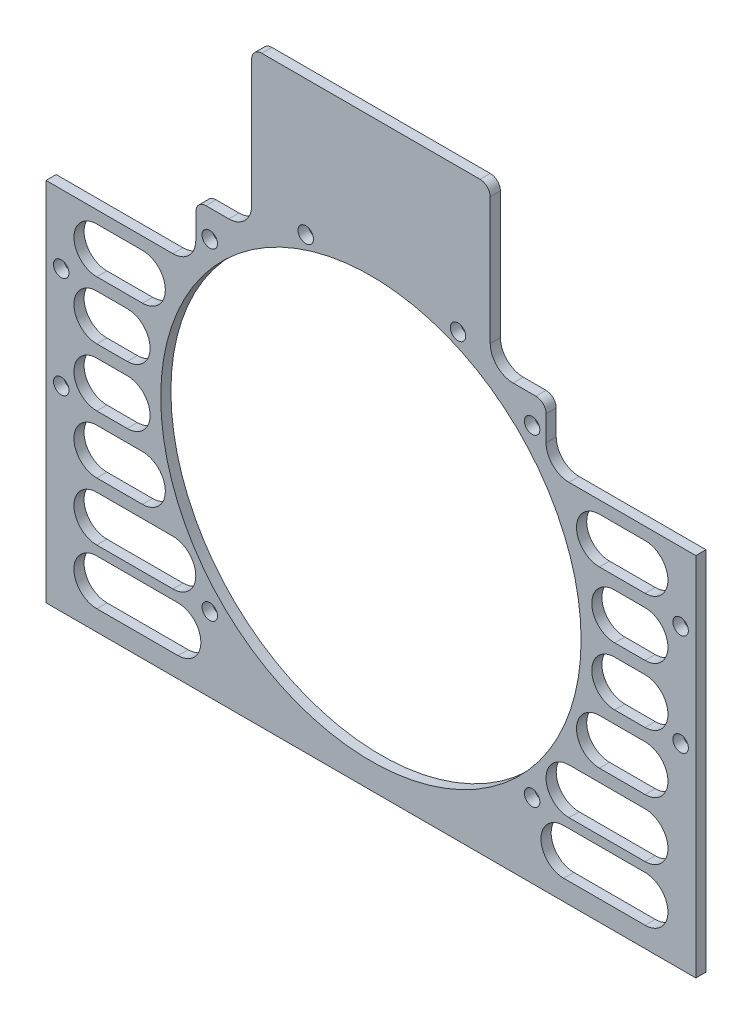
SolidWorks part; units mm, degrees
material "Thornel Mat VMA"
ref_plane "前视基准面" through (0, 0, 0) normal (0, 0, 1) x (1, 0, 0)
ref_plane "上视基准面" through (0, 0, 0) normal (0, 1, 0) x (1, 0, 0)
ref_plane "右视基准面" through (0, 0, 0) normal (1, 0, 0) x (0, 0, -1)
sketch "草图1" plane through (0, 0, 0) normal (0, 0, 1) x (1, 0, 0)
  line L1 (0, 0) -> (128, 0)
  line L2 (0, 0) -> (0, 115)
  line L3 (0, 115) -> (128, 115)
  line L4 (128, 0) -> (128, 115)
  line L6 (3, 115) -> (3, 58.5) construction
  line L7 (3, 58.5) -> (3, 38.5) construction
  line L8 (64, 115) -> (64, 243) construction
  circle A0 centre (3, 58.5) radius 1.525
  circle A1 centre (3, 38.5) radius 1.525
  circle A2 centre (125, 38.5) radius 1.525
  circle A3 centre (125, 58.5) radius 1.525
  dimension "D7" = 3.05
  dimension "D1" = 115
  dimension "D2" = 38.5
  dimension "D3" = 128
  dimension "D4" = 3
  dimension "D6" = 20
extrude "凸台-拉伸1" add sketch "草图1" along normal blind 2
sketch "草图2" plane through (0, 0, 2) normal (0, 0, 1) x (1, 0, 0)
  line L0 (64, 46.4) -> (64, 115) construction
  line L1 (128, 115) -> (0, 115) construction
  line L2 (0, 0) -> (128, 0) construction
  circle A0 centre (64, 46.4) radius 41.4
  dimension "D1" = 82.8
  dimension "D2" = 46.4
extrude "切除-拉伸1" cut sketch "草图2" against normal blind 10
sketch "草图3" plane through (0, 0, 0) normal (0, 0, -1) x (-1, 0, 0)
  line L0 (-64, 46.4) -> (-51.1649, 88.3818) construction
  line L1 (-64, 46.4) -> (-81.1531, 86.8102) construction
  line L2 (-64, 46.4) -> (-64, 115) construction
  line L3 (-128, 115) -> (0, 115) construction
  circle A0 centre (-81.1531, 86.8102) radius 1.525
  circle A1 centre (-51.1649, 88.3818) radius 1.525
  circle A2 centre (-64, 46.4) radius 44.9 construction
  circle A3 centre (-95.7491, 78.1491) radius 1.525
  circle A4 centre (-32.2509, 78.1491) radius 1.525
  circle A5 centre (-32.2509, 14.6509) radius 1.525
  circle A6 centre (-95.7491, 14.6509) radius 1.525
  point P21 (-64, 46.4)
  dimension "D4" = 3.05
  dimension "D5" = 89.8
  dimension "D1" = 43.9
  dimension "D2" = 17
  dimension "D3" = 40
  dimension "D6" = 4
extrude "切除-拉伸2" cut sketch "草图3" against normal blind 10
sketch "草图4" plane through (0, 0, 0) normal (0, 0, -1) x (-1, 0, 0)
  line L0 (-118, 88) -> (-92, 88) construction
  line L1 (-118, 92.5) -> (-92, 92.5)
  line L2 (-118, 83.5) -> (-92, 83.5)
  line L4 (-128, 0) -> (-128, 115) construction
  line L5 (-118, 76.5595) -> (-103, 76.5595) construction
  line L6 (-118, 81.0595) -> (-103, 81.0595)
  line L7 (-118, 72.0595) -> (-103, 72.0595)
  line L8 (-118, 65.119) -> (-109, 65.119) construction
  line L9 (-118, 69.619) -> (-109, 69.619)
  line L10 (-118, 60.619) -> (-109, 60.619)
  line L11 (-118, 53.6786) -> (-112, 53.6786) construction
  line L12 (-118, 58.1786) -> (-112, 58.1786)
  line L13 (-118, 49.1786) -> (-112, 49.1786)
  line L14 (-118, 88) -> (-118, 76.5595) construction
  line L17 (-118, 76.5595) -> (-118, 65.119) construction
  line L18 (-118, 65.119) -> (-118, 53.6786) construction
  line L19 (-128, 47.9583) -> (-156.1739, 47.9583) construction
  line L20 (-118, 8.5) -> (-102, 8.5) construction
  line L21 (-118, 4) -> (-102, 4)
  line L22 (-118, 13) -> (-102, 13)
  line L23 (-118, 19.3571) -> (-103, 19.3571) construction
  line L24 (-118, 14.8571) -> (-103, 14.8571)
  line L25 (-118, 23.8571) -> (-103, 23.8571)
  line L26 (-118, 30.7976) -> (-109, 30.7976) construction
  line L27 (-118, 26.2976) -> (-109, 26.2976)
  line L28 (-118, 35.2976) -> (-109, 35.2976)
  line L29 (-118, 42.2381) -> (-112, 42.2381) construction
  line L30 (-118, 37.7381) -> (-112, 37.7381)
  line L31 (-118, 46.7381) -> (-112, 46.7381)
  line L32 (-118, 53.6786) -> (-118, 42.2381) construction
  line L33 (-64, 87.8) -> (-64, 5) construction
  line L34 (-10, 88) -> (-36, 88) construction
  line L35 (-10, 92.5) -> (-36, 92.5)
  line L36 (-10, 83.5) -> (-36, 83.5)
  line L37 (-10, 76.5595) -> (-25, 76.5595) construction
  line L38 (-10, 81.0595) -> (-25, 81.0595)
  line L39 (-10, 72.0595) -> (-25, 72.0595)
  line L40 (-10, 65.119) -> (-19, 65.119) construction
  line L41 (-10, 69.619) -> (-19, 69.619)
  line L42 (-10, 60.619) -> (-19, 60.619)
  line L43 (-10, 53.6786) -> (-16, 53.6786) construction
  line L44 (-10, 58.1786) -> (-16, 58.1786)
  line L45 (-10, 49.1786) -> (-16, 49.1786)
  line L46 (-10, 8.5) -> (-26, 8.5) construction
  line L47 (-10, 4) -> (-26, 4)
  line L48 (-10, 13) -> (-26, 13)
  line L49 (-10, 19.3571) -> (-25, 19.3571) construction
  line L50 (-10, 14.8571) -> (-25, 14.8571)
  line L51 (-10, 23.8571) -> (-25, 23.8571)
  line L52 (-10, 30.7976) -> (-19, 30.7976) construction
  line L53 (-10, 26.2976) -> (-19, 26.2976)
  line L54 (-10, 35.2976) -> (-19, 35.2976)
  line L55 (-10, 42.2381) -> (-16, 42.2381) construction
  line L56 (-10, 37.7381) -> (-16, 37.7381)
  line L57 (-10, 46.7381) -> (-16, 46.7381)
  line L58 (-10, 53.6786) -> (-10, 42.2381) construction
  line L59 (0, 47.9583) -> (28.1739, 47.9583) construction
  line L60 (-10, 65.119) -> (-10, 53.6786) construction
  line L61 (-10, 76.5595) -> (-10, 65.119) construction
  line L62 (-10, 88) -> (-10, 76.5595) construction
  line L63 (0, 0) -> (-128, 0) construction
  arc A0 (-118, 92.5) -> (-118, 83.5) centre (-118, 88) ccw
  arc A1 (-92, 83.5) -> (-92, 92.5) centre (-92, 88) ccw
  arc A2 (-118, 81.0595) -> (-118, 72.0595) centre (-118, 76.5595) ccw
  arc A3 (-103, 72.0595) -> (-103, 81.0595) centre (-103, 76.5595) ccw
  arc A4 (-118, 69.619) -> (-118, 60.619) centre (-118, 65.119) ccw
  arc A5 (-109, 60.619) -> (-109, 69.619) centre (-109, 65.119) ccw
  arc A6 (-118, 58.1786) -> (-118, 49.1786) centre (-118, 53.6786) ccw
  arc A7 (-112, 49.1786) -> (-112, 58.1786) centre (-112, 53.6786) ccw
  arc A8 (-118, 4) -> (-118, 13) centre (-118, 8.5) cw
  arc A9 (-102, 13) -> (-102, 4) centre (-102, 8.5) cw
  arc A10 (-118, 14.8571) -> (-118, 23.8571) centre (-118, 19.3571) cw
  arc A11 (-103, 23.8571) -> (-103, 14.8571) centre (-103, 19.3571) cw
  arc A12 (-118, 26.2976) -> (-118, 35.2976) centre (-118, 30.7976) cw
  arc A13 (-109, 35.2976) -> (-109, 26.2976) centre (-109, 30.7976) cw
  arc A14 (-118, 37.7381) -> (-118, 46.7381) centre (-118, 42.2381) cw
  arc A15 (-112, 46.7381) -> (-112, 37.7381) centre (-112, 42.2381) cw
  circle A16 centre (-64, 46.4) radius 41.4 construction
  arc A17 (-10, 92.5) -> (-10, 83.5) centre (-10, 88) cw
  arc A18 (-36, 83.5) -> (-36, 92.5) centre (-36, 88) cw
  arc A19 (-10, 81.0595) -> (-10, 72.0595) centre (-10, 76.5595) cw
  arc A20 (-25, 72.0595) -> (-25, 81.0595) centre (-25, 76.5595) cw
  arc A21 (-10, 69.619) -> (-10, 60.619) centre (-10, 65.119) cw
  arc A22 (-19, 60.619) -> (-19, 69.619) centre (-19, 65.119) cw
  arc A23 (-10, 58.1786) -> (-10, 49.1786) centre (-10, 53.6786) cw
  arc A24 (-16, 49.1786) -> (-16, 58.1786) centre (-16, 53.6786) cw
  arc A25 (-10, 4) -> (-10, 13) centre (-10, 8.5) ccw
  arc A26 (-26, 13) -> (-26, 4) centre (-26, 8.5) ccw
  arc A27 (-10, 14.8571) -> (-10, 23.8571) centre (-10, 19.3571) ccw
  arc A28 (-25, 23.8571) -> (-25, 14.8571) centre (-25, 19.3571) ccw
  arc A29 (-10, 26.2976) -> (-10, 35.2976) centre (-10, 30.7976) ccw
  arc A30 (-19, 35.2976) -> (-19, 26.2976) centre (-19, 30.7976) ccw
  arc A31 (-10, 37.7381) -> (-10, 46.7381) centre (-10, 42.2381) ccw
  arc A32 (-16, 46.7381) -> (-16, 37.7381) centre (-16, 42.2381) ccw
  point P2 (-105, 88)
  point P13 (-110.5, 76.5595)
  point P18 (-113.5, 65.119)
  point P25 (-115, 53.6786)
  point P40 (-110, 8.5)
  point P47 (-110.5, 19.3571)
  point P54 (-113.5, 30.7976)
  point P61 (-115, 42.2381)
  point P74 (-23, 88)
  point P81 (-17.5, 76.5595)
  point P88 (-14.5, 65.119)
  point P95 (-13, 53.6786)
  point P102 (-18, 8.5)
  point P109 (-17.5, 19.3571)
  point P116 (-14.5, 30.7976)
  point P123 (-13, 42.2381)
  dimension "D2" = 4.5
  dimension "D3" = 10
  dimension "D4" = 26
  dimension "D5" = 10.8571
  dimension "D6" = 15
  dimension "D7" = 9
  dimension "D8" = 6
  dimension "D9" = 16
  dimension "D10" = 4
  dimension "D11" = 88
extrude "切除-拉伸3" cut sketch "草图4" against normal blind 10
sketch "草图5" plane through (0, 0, 0) normal (0, 0, -1) x (-1, 0, 0)
  line L0 (-98.5, 76.5595) -> (-98.5, 83.5)
  line L1 (-118, 83.5) -> (-92, 83.5) construction
  line L2 (-98.5, 83.5) -> (-87.5, 88)
  line L3 (-87.5, 88) -> (-87.5, 115)
  line L4 (-128, 115) -> (0, 115) construction
  line L5 (-87.5, 115) -> (-128, 115)
  line L6 (-128, 115) -> (-128, 72.0595)
  line L7 (-128, 0) -> (-128, 115) construction
  line L8 (-128, 72.0595) -> (-103, 72.0595)
  line L9 (-103, 72.0595) -> (-98.5, 76.5595)
  line L10 (-64, 46.4) -> (-64, 87.8) construction
  line L11 (-25, 72.0595) -> (-29.5, 76.5595)
  line L12 (0, 72.0595) -> (-25, 72.0595)
  line L13 (0, 115) -> (0, 72.0595)
  line L14 (-40.5, 115) -> (0, 115)
  line L15 (-40.5, 88) -> (-40.5, 115)
  line L16 (-29.5, 83.5) -> (-40.5, 88)
  line L17 (-29.5, 76.5595) -> (-29.5, 83.5)
  arc A0 (-103, 72.0595) -> (-103, 81.0595) centre (-103, 76.5595) ccw construction
  arc A1 (-92, 83.5) -> (-92, 92.5) centre (-92, 88) ccw construction
  circle A2 centre (-64, 46.4) radius 41.4 construction
extrude "切除-拉伸4" cut sketch "草图5" against normal blind 10
fillet "圆角1" radius 2 4 edges at (29.5, 83.5, 1) (40.5, 115, 1) (87.5, 115, 1) (98.5, 83.5, 1)
